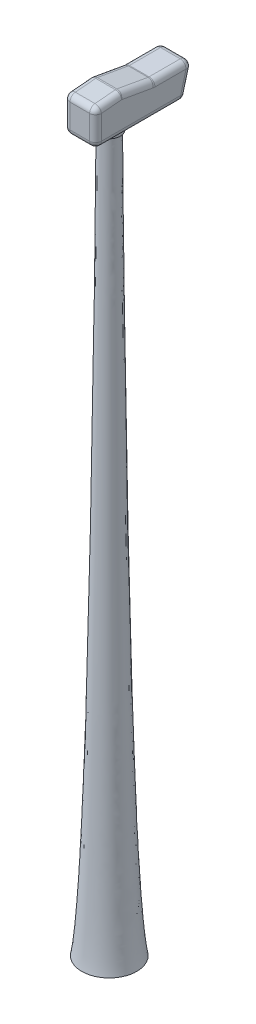
SolidWorks part; units mm, degrees
ref_plane "Ebene vorne" through (0, 0, 0) normal (0, 0, 1) x (1, 0, 0)
ref_plane "Ebene oben" through (0, 0, 0) normal (0, 1, 0) x (1, 0, 0)
ref_plane "Ebene rechts" through (0, 0, 0) normal (1, 0, 0) x (0, 0, -1)
sketch "Skizze2" plane through (0, 0, 0) normal (1, 0, 0) x (0, 0, -1)
  line L0 (2800, -4320) -> (2800, 4320)
  line L1 (-2800, -2400) -> (2800, -2400) construction
  line L2 (-2800, -2400) -> (-2800, 2400) construction
  line L3 (-2800, 2400) -> (2800, 2400) construction
  line L4 (2800, -2400) -> (2800, 2400) construction
  line L5 (-2800, -2400) -> (2800, 2400) construction
  line L6 (-2800, 2400) -> (2800, -2400) construction
  line L7 (2800, 4320) -> (9280, 4886.9265)
  line L8 (9280, 4886.9265) -> (17200, 3490.4169)
  line L9 (17200, 3490.4169) -> (26800, 3490.4169)
  line L10 (26800, 3490.4169) -> (24707.2051, -4320)
  line L11 (24707.2051, -4320) -> (2800, -4320)
  point P0 (0, 0)
  dimension "D1" = 5600
  dimension "D2" = 4800
  dimension "D3" = 95
  dimension "D4" = 165
  dimension "D5" = 75
  dimension "D6" = 6480
  dimension "D7" = 7920
  dimension "D8" = 24000
  dimension "D9" = 1920
  dimension "D10" = 1920
extrude "Aufsatz-Linear austragen1" add sketch "Skizze2" along normal blind 3840 and the other way blind 3840
fillet "Verrundung1" radius 1440 18 edges at (-3840, -414.7916, -25753.6026) (-3840, -4320, -13753.6026) (0, -4320, -24707.2051) (-3840, 3490.4169, -22000) (0, 3490.4169, -26800) (-3840, 4188.6717, -13240) (0, 3490.4169, -17200) (3840, 4188.6717, -13240) (3840, 3490.4169, -22000) (3840, -414.7916, -25753.6026) (3840, -4320, -13753.6026) (-3840, 4603.4633, -6040) (0, 4886.9265, -9280) (3840, 4603.4633, -6040) (-3840, 0, -2800) (0, 4320, -2800) (3840, 0, -2800) (0, -4320, -2800)
sketch "Skizze3" plane through (0, 0, 0) normal (1, 0, 0) x (0, 0, -1)
  line L0 (-28.6725, 0) -> (353.0024, 0) construction
  line L1 (10000, 0) -> (10000, -116.2223) construction
  line L2 (10000, -2880) -> (7312, -2880)
  line L3 (4240, -2880) -> (23602.2542, -2880) construction
  line L4 (7312, -2880) -> (7312, -5280)
  line L5 (7312, -5280) -> (7552, -5280)
  line L6 (7552, -5280) -> (7552, -4320)
  line L7 (23602.2542, -4320) -> (4240, -4320) construction
  line L8 (7552, -4320) -> (7696, -4320)
  line L9 (7696, -4320) -> (7696, -5280)
  line L10 (10000, -2880) -> (10000, -180000)
  line L11 (10000, -180000) -> (3280, -180000)
  line L12 (2800, -2880) -> (2800, 3000.4831) construction
  line L13 (4515.5909, -5280) -> (4653.532, -5280) construction
  spline S0 degree 3 poles (7696, -5280) (7696, -6007.7736) (6760.6585, -162191.9892) (3280, -180000) knots 0 0 0 0 1 1 1 1
  dimension "D1" = 2400
  dimension "D2" = 7200
  dimension "D3" = 2688
  dimension "D4" = 240
  dimension "D5" = 144
  dimension "D6" = 3600
  dimension "D7" = 180000
  dimension "D8" = 108000
  dimension "D9" = 6720
revolve "Rotation1" add sketch "Skizze3" angle 360 about L1
